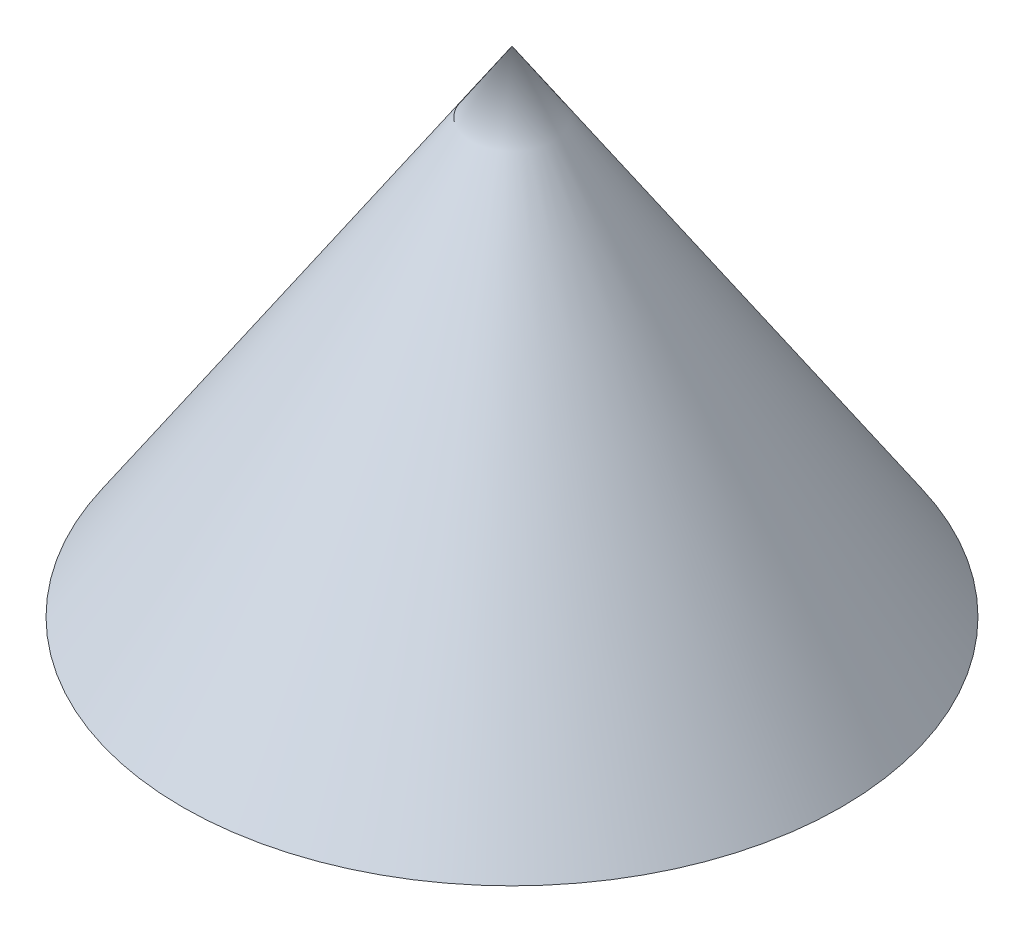
SolidWorks part; units mm, degrees
ref_plane "Front Plane" through (0, 0, 0) normal (0, 0, 1) x (1, 0, 0)
ref_plane "Top Plane" through (0, 0, 0) normal (0, 1, 0) x (1, 0, 0)
ref_plane "Right Plane" through (0, 0, 0) normal (1, 0, 0) x (0, 0, -1)
sketch "Sketch1" plane through (0, 0, 0) normal (0, 0, 1) x (1, 0, 0)
  line L0 (0, 0) -> (0, 105)
  line L1 (0, 105) -> (70, 0)
  line L2 (70, 0) -> (0, 0)
  dimension "D1" = 70
  dimension "D2" = 105
revolve "Revolve1" add sketch "Sketch1" angle 360 about L0
ref_axis "Axis1" through (0, 105, 0) along (0, -1, 0)
